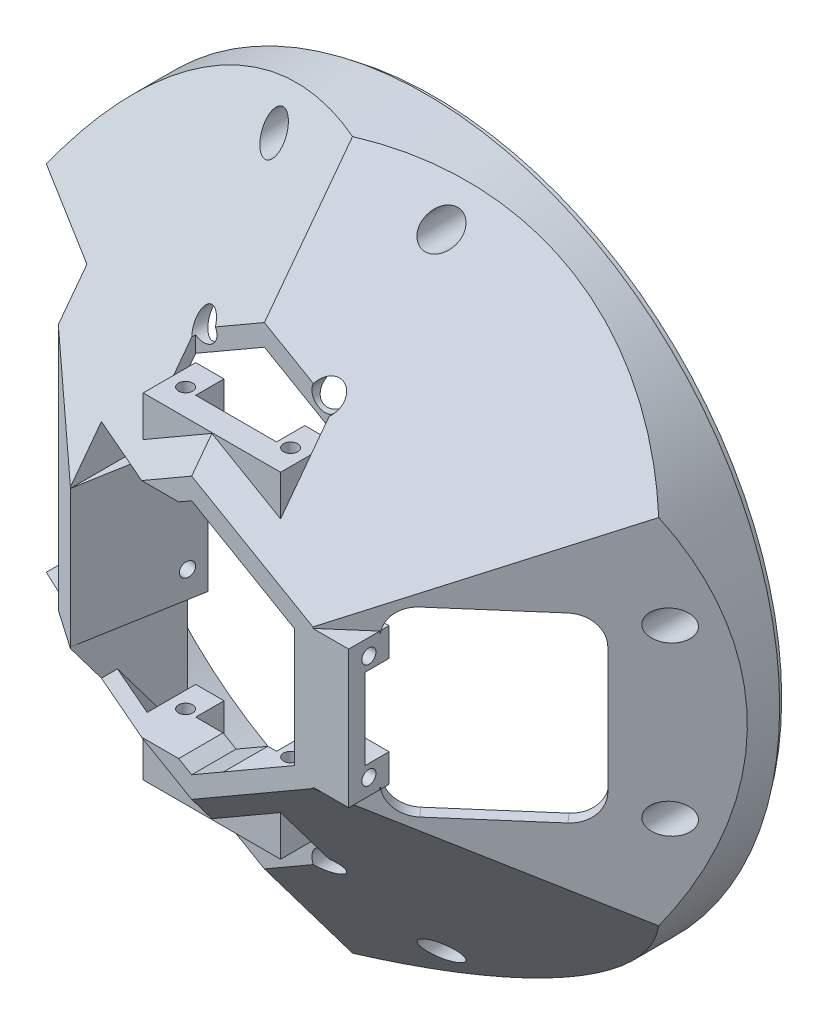
SolidWorks part; units mm, degrees
ref_plane "Front Plane" through (0, 0, 0) normal (0, 0, 1) x (1, 0, 0)
ref_plane "Top Plane" through (0, 0, 0) normal (0, 1, 0) x (1, 0, 0)
ref_plane "Right Plane" through (0, 0, 0) normal (1, 0, 0) x (0, 0, -1)
sketch "Sketch1" plane through (0, 0, 0) normal (0, 0, 1) x (1, 0, 0)
  circle A0 centre (0, 0) radius 87.5
  dimension "D1" = 175
extrude "Boss-Extrude1" add sketch "Sketch1" along normal blind 60
sketch "Sketch2" plane through (0, 0, 0) normal (0, 1, 0) x (1, 0, 0)
  line L0 (-73.4655, -109.9854) -> (-130.9655, -59.9854)
  line L1 (-73.4655, -109.9854) -> (-30, -60)
  line L2 (-130.9655, -59.9854) -> (-87.5, -10)
  line L3 (-30, -60) -> (-87.5, -10)
  line L4 (-73.4655, -109.9854) -> (-87.5, -10) construction
  line L5 (-130.9655, -59.9854) -> (-30, -60) construction
  line L7 (-87.5, 0) -> (-87.5, -60) construction
  line L8 (-87.5, -60) -> (87.5, -60) construction
  point P1 (-80.4828, -59.9927)
  dimension "D1" = 30
  dimension "D2" = 10
extrude "Cut-Extrude1" cut sketch "Sketch2" against normal through all and the other way through all
pattern_circular "CirPattern1" count 6 over 360 about axis through (0, 0, 0) along (0, 0, 1) of "Cut-Extrude1"
shell "Shell1" thickness 3 removed face at (87.5, 0, 0) removed face at (0, 0, 60)
sketch "Sketch3" plane through (0, 0, 0) normal (0, 0, -1) x (-1, 0, 0)
  circle A0 centre (0, 0) radius 87.5 construction
  circle A1 centre (0, 0) radius 87.5
  circle A2 centre (0, 0) radius 86
  dimension "D1" = 1.5
extrude "Cut-Extrude2" cut sketch "Sketch3" against normal blind 2
sketch "Sketch4" plane through (0, 0, 0) normal (0, 0, 1) x (1, 0, 0)
  line L8 (-53, 40) -> (-53, -40)
  line L9 (-30, -17.3205) -> (-30, 17.3205) construction
  line L10 (-75.7772, 43.75) -> (-53, 40)
  line L11 (-53, -40) -> (-75.7772, -43.75)
  line L12 (-53, 0) -> (0, 0) construction
  arc A1 (-75.7772, 43.75) -> (-75.7772, -43.75) centre (0, 0) ccw construction
  arc A2 (-75.7772, 43.75) -> (-75.7772, -43.75) centre (0, 0) ccw
  dimension "D1" = 23
  dimension "D2" = 80
extrude "Cut-Extrude3" cut sketch "Sketch4" along normal through all
sketch "Sketch5" plane through (0, 0, 0) normal (0, 0, 1) x (1, 0, 0)
  line L0 (0, 0) -> (-20.7055, 77.2741) construction
  line L1 (0, 84.5) -> (0, 29.3618) construction
  line L2 (-23.5083, 73.1335) -> (-31.3758, 78.459)
  line L3 (-16.208, 75.0896) -> (-12.0573, 83.6354)
  line L4 (-31.3758, 78.459) -> (-12.0573, 83.6354) construction
  line L5 (-21.7165, 81.0472) -> (-20.7055, 77.2741) construction
  arc A0 (-23.5083, 73.1335) -> (-16.208, 75.0896) centre (-20.7055, 77.2741) ccw
  arc A1 (-72.6058, -43.2279) -> (-72.6058, 43.2279) centre (0, 0) ccw construction
  arc A2 (0, 84.5) -> (-72.6058, 43.2279) centre (0, 0) ccw construction
  arc A3 (-12.0573, 83.6354) -> (-31.3758, 78.459) centre (0, 0) ccw
  dimension "D2" = 10
  dimension "D1" = 15
  dimension "D3" = 80
  dimension "D4" = 20
extrude "Boss-Extrude2" add sketch "Sketch5" along normal up to next
sketch "Sketch6" plane through (0, 0, 0) normal (0, 0, -1) x (-1, 0, 0)
  circle A0 centre (20.7055, 77.2741) radius 1.75
  dimension "D1" = 3.5
extrude "Cut-Extrude4" cut sketch "Sketch6" against normal through all
sketch "Sketch7" plane through (0, 0, 60) normal (0, 0, 1) x (1, 0, 0)
  circle A2 centre (-20.7055, 77.2741) radius 3.75
  circle A3 centre (-20.7055, 77.2741) radius 3.75
  dimension "D1" = 2
extrude "Cut-Extrude5" cut sketch "Sketch7" against normal blind 55
mirror "Mirror1" about plane through (0, 0, 0) normal (1, 0, 0) of "Cut-Extrude5", "Cut-Extrude4", "Boss-Extrude2"
pattern_circular "CirPattern2" count 3 every 90 about axis through (0, 0, 2) along (0, 0, -1) of "Mirror1"
sketch "Sketch8" plane through (42.6265, 0, 49.0205) normal (0.6562, 0, 0.7546) x (0.7546, 0, -0.6562)
  line L0 (0, 0) -> (15, 0) construction
  line L1 (2, 22.5) -> (28, 22.5)
  line L2 (-5, 15.5) -> (-5, -15.5)
  line L3 (2, -22.5) -> (28, -22.5)
  line L4 (35, 15.5) -> (35, -15.5)
  line L5 (-5, 22.5) -> (35, -22.5) construction
  line L6 (-5, -22.5) -> (35, 22.5) construction
  arc A0 (-5, -15.5) -> (2, -22.5) centre (2, -15.5) ccw
  arc A1 (28, -22.5) -> (35, -15.5) centre (28, -15.5) ccw
  arc A2 (28, 22.5) -> (35, 15.5) centre (28, 15.5) cw
  arc A3 (2, 22.5) -> (-5, 15.5) centre (2, 15.5) ccw
  point P0 (15, 0)
  dimension "D4" = 7
  dimension "D1" = 45
  dimension "D2" = 40
  dimension "D3" = 15
extrude "Cut-Extrude6" cut sketch "Sketch8" against normal through all
sketch "Sketch10" plane through (0, 0, 0) normal (0, 1, 0) x (1, 0, 0)
  line L0 (0, -20.1937) -> (0, -60) construction
  line L1 (-17, -42) -> (17, -42)
  line L2 (-17, -42) -> (-17, -55)
  line L3 (-17, -55) -> (17, -55)
  line L4 (17, -42) -> (17, -55)
  line L5 (-17, -42) -> (17, -55) construction
  line L6 (-17, -55) -> (17, -42) construction
  line L7 (0, -48.5) -> (0, 0) construction
  line L8 (0, -60) -> (30, -60) construction
  point P0 (0, -48.5)
  dimension "D1" = 13
  dimension "D2" = 34
  dimension "D3" = 5
extrude "Cut-Extrude8" cut sketch "Sketch10" against normal through all
sketch "Sketch12" plane through (0, 0, 42) normal (0, 0, 1) x (1, 0, 0)
  line L0 (17, -31.4656) -> (17, -48.7284) construction
  line L1 (-17, -31.4656) -> (17, -31.4656)
  line L2 (-17, -31.4656) -> (-17, -24.8261)
  line L4 (17, -31.4656) -> (17, -24.8261)
  line L5 (0, -41.2805) -> (17, -31.4656) construction
  line L6 (30, -17.3205) -> (0, -34.641) construction
  line L7 (0, -34.641) -> (-30, -17.3205) construction
  line L8 (-17, -24.8261) -> (-7.8561, -24.8261)
  line L9 (0, -29.3618) -> (-25.4281, -14.6809) construction
  line L10 (-7.8561, -24.8261) -> (0, -29.3618)
  line L11 (0, -29.3618) -> (7.8561, -24.8261)
  line L12 (25.4281, -14.6809) -> (0, -29.3618) construction
  line L13 (7.8561, -24.8261) -> (17, -24.8261)
extrude "Boss-Extrude4" add sketch "Sketch12" along normal up to next
sketch "Sketch13" plane through (0, -31.4656, 0) normal (0, -1, 0) x (1, 0, 0)
  line L0 (0, 42) -> (-17, 42) construction
  line L1 (-10, 42) -> (10, 42)
  line L2 (-10, 42) -> (-10, 49)
  line L3 (-10, 49) -> (10, 49)
  line L4 (10, 42) -> (10, 49)
  line L5 (0, 49) -> (0, 60) construction
  line L6 (-13, 48.5) -> (-17, 48.5) construction
  line L9 (-13, 48.5) -> (13, 48.5) construction
  line L10 (-17, 42) -> (-17, 55) construction
  line L11 (13, 48.5) -> (17, 48.5) construction
  line L12 (17, 55) -> (17, 42) construction
  circle A0 centre (-13, 48.5) radius 1.75
  circle A1 centre (13, 48.5) radius 1.75
  point P9 (0, 48.5)
  point P20 (0, 0)
  dimension "D4" = 3.5
  dimension "D1" = 7
  dimension "D2" = 20
  dimension "D3" = 26
extrude "Cut-Extrude9" cut sketch "Sketch13" against normal blind 8
sketch "Sketch14" plane through (0, -31.4656, 0) normal (0, -1, 0) x (1, 0, 0)
  line L13 (-17, 42) -> (-10, 42)
  line L14 (-10, 42) -> (-10, 49)
  line L15 (-10, 49) -> (10, 49)
  line L16 (10, 49) -> (10, 42)
  line L17 (10, 42) -> (17, 42)
  line L18 (17, 42) -> (17, 51.0244)
  line L19 (17, 51.0244) -> (17, 55)
  line L20 (17, 55) -> (7.8561, 55)
  line L21 (7.8561, 55) -> (0, 58.4157)
  line L22 (0, 58.4157) -> (-7.8561, 55)
  line L23 (-7.8561, 55) -> (-17, 55)
  line L24 (-17, 55) -> (-17, 51.0244)
  line L25 (-17, 51.0244) -> (-17, 42)
  line L26 (-17, 42) -> (-10, 42)
  line L27 (-10, 42) -> (-10, 49)
  line L28 (-10, 49) -> (10, 49)
  line L29 (10, 49) -> (10, 42)
  line L30 (10, 42) -> (17, 42)
  line L31 (17, 42) -> (17, 51.0244)
  line L32 (17, 51.0244) -> (17, 55)
  line L33 (17, 55) -> (-7.8561, 55)
  line L36 (-7.8561, 55) -> (-17, 55)
  line L37 (-17, 55) -> (-17, 51.0244)
  line L38 (-17, 51.0244) -> (-17, 42)
  circle A0 centre (13, 48.5) radius 1.75 construction
  circle A1 centre (-13, 48.5) radius 1.75 construction
  circle A2 centre (13, 48.5) radius 1.75
  circle A3 centre (-13, 48.5) radius 1.75
  point P2 (-7.6372, 55)
  dimension "D1" = 0
extrude "Boss-Extrude5" add sketch "Sketch14" along normal blind 10
mirror "Mirror2" about plane through (0, 0, 0) normal (0, 1, 0) of "Boss-Extrude5", "Cut-Extrude8", "Boss-Extrude4", "Cut-Extrude9"
sketch "Sketch15" plane through (0, 0, 0) normal (0, 0, 1) x (1, 0, 0)
  line L1 (-15, 50) -> (15, 50) construction
  line L2 (-15, 50) -> (-15, -50) construction
  line L3 (-15, -50) -> (15, -50) construction
  line L4 (15, 50) -> (15, -50) construction
  line L5 (-15, 50) -> (15, -50) construction
  line L6 (-15, -50) -> (15, 50) construction
  circle A0 centre (-15, 50) radius 3.25
  circle A1 centre (15, 50) radius 3.25
  circle A2 centre (15, -50) radius 3.25
  circle A3 centre (-15, -50) radius 3.25
  point P0 (0, 0)
  dimension "D1" = 6.5
  dimension "D2" = 100
  dimension "D3" = 30
extrude "Cut-Extrude10" cut sketch "Sketch15" along normal through all
sketch "Sketch16" plane through (0, 0, 60) normal (0, 0, 1) x (1, 0, 0)
  line L0 (25.4281, 14.6809) -> (25.4281, -14.6809) construction
  line L1 (25.4281, -17) -> (38.8535, -17)
  line L2 (25.4281, -17) -> (25.4281, 17)
  line L3 (25.4281, 17) -> (38.8535, 17)
  line L4 (38.8535, -17) -> (38.8535, 17)
  line L5 (38.8535, 15.5) -> (38.8535, -15.5) construction
  line L6 (25.4281, 0) -> (0, 0) construction
  dimension "D1" = 34
extrude "Boss-Extrude6" add sketch "Sketch16" against normal blind 10
sketch "Sketch17" plane through (38.8535, 0, 0) normal (1, 0, 0) x (0, 0, -1)
  line L0 (-55, 13) -> (-55, -13) construction
  line L1 (-55, 0) -> (0, 0) construction
  line L2 (-60, -17) -> (-60, 17) construction
  line L3 (-56, 10) -> (-46.4829, 10)
  line L4 (-56, 10) -> (-56, -10)
  line L5 (-56, -10) -> (-46.4829, -10)
  line L6 (-46.4829, 10) -> (-46.4829, -10)
  circle A0 centre (-55, 13) radius 1.75
  circle A1 centre (-55, -13) radius 1.75
  point P11 (-46.4829, 0)
  dimension "D5" = 3.5
  dimension "D1" = 26
  dimension "D2" = 20
  dimension "D3" = 1
  dimension "D4" = 5
extrude "Cut-Extrude11" cut sketch "Sketch17" against normal blind 37
sketch "Sketch18" plane through (0, 0, 60) normal (0, 0, 1) x (1, 0, 0)
  line L0 (-3.2248, 0) -> (0, 0) construction
  line L1 (-30, 27.5) -> (-3.2248, 27.5)
  line L2 (-30, 27.5) -> (-30, -27.5)
  line L3 (-30, -27.5) -> (-3.2248, -27.5)
  line L4 (-3.2248, 27.5) -> (-3.2248, -27.5)
  line L5 (0, -29.3618) -> (-7.8561, -24.8261) construction
  point P7 (-15, 0)
  point P8 (-15, -27.0939)
  point P10 (-7.7907, -27.0939)
  point P11 (-3.157, -27.5391)
  dimension "D1" = 55
extrude "Cut-Extrude12" cut sketch "Sketch18" against normal blind 37
sketch "Sketch19" plane through (0, 0, 0) normal (0, 1, 0) x (1, 0, 0)
  line L0 (-30, -56.0244) -> (-30, -31.0244)
  line L1 (-30, -31.0244) -> (-35, -31.0244)
  line L2 (-35, -31.0244) -> (-35, -51.6766)
  line L3 (-53, -36.0244) -> (-30, -56.0244) construction
  line L4 (-35, -51.6766) -> (-30, -56.0244)
  dimension "D1" = 25
  dimension "D2" = 5
extrude "Boss-Extrude7" add sketch "Sketch19" along normal up to next and the other way up to next
sketch "Sketch20" plane through (0, 0, 0) normal (0, 1, 0) x (1, 0, 0)
  line L0 (-30, -31.0244) -> (-24.8908, -31.0244)
  line L1 (-24.8908, -31.0244) -> (-30, -60)
  line L2 (-30, -60) -> (-30, -31.0244)
  dimension "D1" = 10
extrude "Boss-Extrude8" add sketch "Sketch20" along normal blind 17 and the other way blind 17
sketch "Sketch21" plane through (-18.8348, 0, -3.3211) normal (0.9848, 0, 0.1736) x (0.1736, 0, -0.9848)
  line L0 (-39.2979, 10.5) -> (-39.2979, -10.5) construction
  line L1 (-64.2979, -17) -> (-64.2979, 17) construction
  line L3 (-39.2979, 0) -> (0, 0) construction
  circle A0 centre (-39.2979, 10.5) radius 1.75
  circle A1 centre (-39.2979, -10.5) radius 1.75
  dimension "D1" = 3.5
  dimension "D2" = 21
  dimension "D3" = 25
extrude "Cut-Extrude13" cut sketch "Sketch21" against normal blind 25
